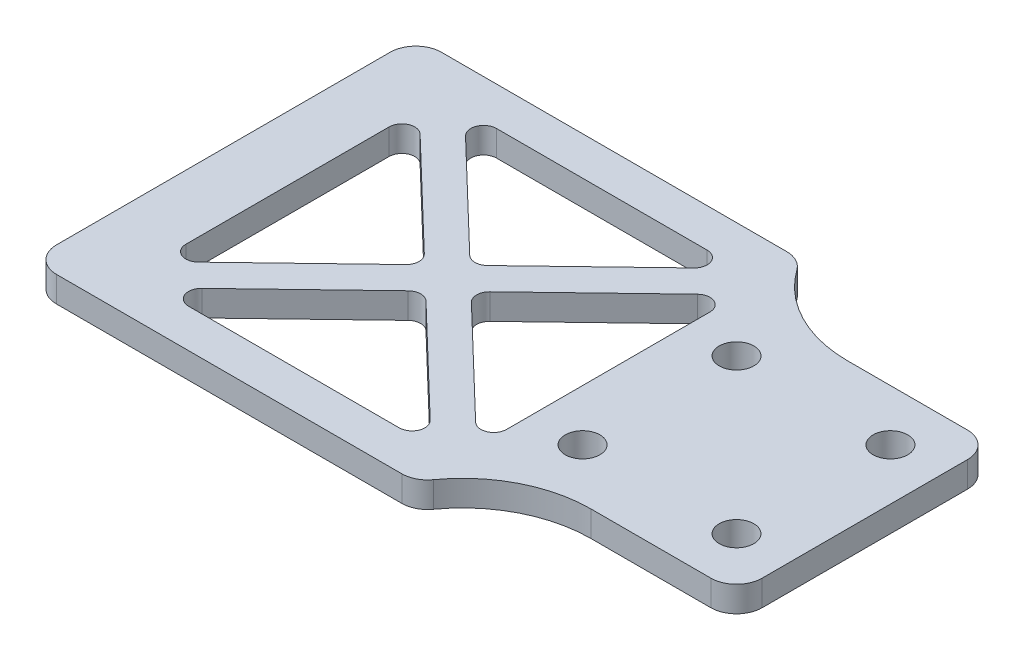
SolidWorks part; units mm, degrees
material "碳纤维"
ref_plane "前视基准面" through (0, 0, 0) normal (0, 0, 1) x (1, 0, 0)
ref_plane "上视基准面" through (0, 0, 0) normal (0, 1, 0) x (1, 0, 0)
ref_plane "右视基准面" through (0, 0, 0) normal (1, 0, 0) x (0, 0, -1)
sketch "草图1" plane through (0, 0, 0) normal (0, 1, 0) x (1, 0, 0)
  line L1 (-10, -10) -> (10, -10)
  line L2 (-10, -10) -> (-10, 10)
  line L3 (-10, 10) -> (10, 10)
  line L4 (10, -10) -> (10, 10)
  line L5 (0, 10) -> (0, -10) construction
  line L6 (-10, 0) -> (10, 0) construction
  circle A0 centre (-6, 6) radius 1.35
  circle A1 centre (6, 6) radius 1.35
  circle A2 centre (6, -6) radius 1.35
  circle A3 centre (-6, -6) radius 1.35
  point P0 (0, 0)
  point P12 (0, 0)
  point P13 (0, 0)
  dimension "D4" = 2.7
  dimension "D1" = 12
  dimension "D2" = 12
  dimension "D3" = 20
  dimension "D5" = 10
  dimension "D6" = 10
extrude "凸台-拉伸1" add sketch "草图1" along normal blind 2
sketch "草图2" plane through (0, 2, 0) normal (0, 1, 0) x (1, 0, 0)
  line L0 (-10, 10) -> (-10, -10) construction
  line L1 (-40, -15) -> (-10, -15)
  line L2 (-40, -15) -> (-40, 15)
  line L3 (-40, 15) -> (-10, 15)
  line L4 (-10, -15) -> (-10, 15)
  line L5 (-25, 15) -> (-25, -15) construction
  line L6 (-40, 0) -> (-10, 0) construction
  point P0 (-25, 0)
  dimension "D1" = 30
  dimension "D2" = 30
extrude "凸台-拉伸2" add sketch "草图2" against normal up to surface (2 mm away) up to face at (6, 0, 7.35)
fillet "圆角1" radius 10 2 edges at (-10, 1, -10) (-10, 1, 10)
sketch "草图3" plane through (0, 0, 0) normal (0, -1, 0) x (1, 0, 0)
  line L0 (-35, 0) -> (-10, 0) construction
  line L1 (-10, -12) -> (-35, -12) construction
  line L2 (-10, -12) -> (-10, 12) construction
  line L3 (-10, 12) -> (-35, 12) construction
  line L4 (-35, -12) -> (-35, 12) construction
  line L5 (-22.5, 0) -> (-10, -12) construction
  line L6 (-22.5, 0) -> (-22.5, -12) construction
  line L7 (-11.805, -12) -> (-22.5, -1.7328)
  line L8 (-22.5, -1.7328) -> (-33.195, -12)
  line L9 (-33.195, -12) -> (-11.805, -12)
  line L10 (-10, -10.2672) -> (-20.695, 0)
  line L11 (-20.695, 0) -> (-10, 10.2672)
  line L12 (-10, 10.2672) -> (-10, -10.2672)
  line L13 (-40, -15) -> (-40, 15) construction
  line L14 (-40, 15) -> (-10, 15) construction
  line L15 (-33.195, 12) -> (-11.805, 12)
  line L16 (-22.5, 1.7328) -> (-33.195, 12)
  line L17 (-11.805, 12) -> (-22.5, 1.7328)
  line L18 (-24.305, 0) -> (-35, 10.2672)
  line L19 (-35, -10.2672) -> (-24.305, 0)
  line L20 (-35, 10.2672) -> (-35, -10.2672)
  circle A0 centre (-6, -6) radius 1.35 construction
  point P18 (-9.861, -12.6156)
  point P23 (-50.3325, -12)
  point P24 (-11.9865, -11.8258)
  dimension "D1" = 5
  dimension "D2" = 2.5
  dimension "D3" = 3
  dimension "D4" = 4
extrude "切除-拉伸1" cut sketch "草图3" against normal blind 10
fillet "圆角2" radius 1 12 edges at (-22.5, 1, -1.7328) (-11.805, 1, -12) (-33.195, 1, -12) (-35, 1, 10.2672) (-24.305, 1, 0) (-35, 1, -10.2672) (-20.695, 1, 0) (-10, 1, 10.2672) (-11.805, 1, 12) (-22.5, 1, 1.7328) (-33.195, 1, 12) (-10, 1, -10.2672)
fillet "圆角3" radius 2 6 edges at (10, 1, 10) (-10, 1, 15) (-40, 1, 15) (-40, 1, -15) (-10, 1, -15) (10, 1, -10)
